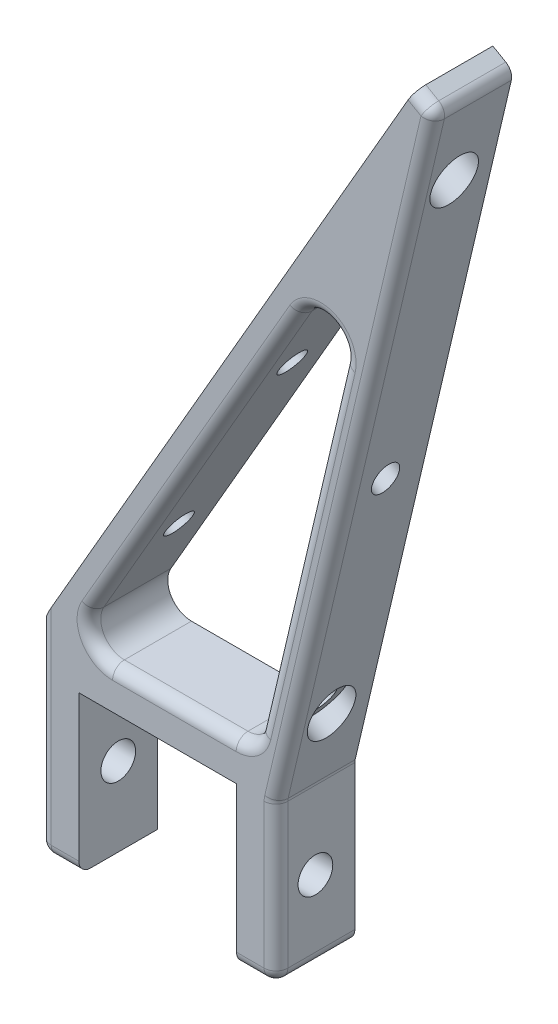
SolidWorks part; units mm, degrees
material "ABS"
ref_plane "Front Plane" through (0, 0, 0) normal (0, 0, 1) x (1, 0, 0)
ref_plane "Top Plane" through (0, 0, 0) normal (0, 1, 0) x (1, 0, 0)
ref_plane "Right Plane" through (0, 0, 0) normal (1, 0, 0) x (0, 0, -1)
sketch "Sketch1" plane through (0, 0, 0) normal (0, 0, 1) x (1, 0, 0)
  line L0 (-10, -20) -> (-10, 0)
  line L1 (-10, 0) -> (10, 0)
  line L2 (10, 0) -> (10, -20)
  line L3 (10, -20) -> (15, -20)
  line L4 (15, -20) -> (15, 0)
  line L5 (15, 0) -> (35.1015, 85.7704)
  line L6 (32.5, 87.2724) -> (-15, 5)
  line L7 (-15, 5) -> (-15, -20)
  line L8 (-15, -20) -> (-10, -20)
  line L9 (32.5, 87.2724) -> (35.1015, 85.7704)
  dimension "D1" = 5
  dimension "D2" = 20
  dimension "D3" = 20
  dimension "D4" = 166.81
  dimension "D5" = 150
  dimension "D6" = 20
  dimension "D7" = 25
  dimension "D8" = 95
extrude "Boss-Extrude1" add sketch "Sketch1" along normal blind 10
sketch "Sketch2" plane through (0, 0, 10) normal (0, 0, 1) x (1, 0, 0)
  line L0 (-10.9175, 5) -> (28.2148, 72.7791)
  line L1 (28.2148, 72.7791) -> (12.3298, 5)
  line L2 (12.3298, 5) -> (-10.9175, 5)
  line L3 (-10, 0) -> (10, 0) construction
  line L5 (15, 0) -> (35.1015, 85.7704) construction
  line L6 (32.5, 87.2724) -> (-15, 5) construction
  dimension "D1" = 5
  dimension "D2" = 3.7406
  dimension "D3" = 3.5356
extrude "Cut-Extrude1" cut sketch "Sketch2" against normal through all
fillet "Fillet1" radius 3 3 edges at (-10.9175, 5, 5) (12.3298, 5, 5) (28.2148, 72.7791, 5)
fillet "Fillet2" radius 1.5 16 edges at (35.1015, 85.7704, 5) (-15, -7.5, 10) (33.8007, 86.5214, 10) (25.0507, 42.8852, 10) (15, -10, 10) (12.5, -20, 10) (-12.5, -20, 10) (21.7651, 56.485, 10) (4.8718, 32.3478, 10) (-8.3194, 6.5, 10) (2.1151, 5, 10) (11.8153, 5.6491, 10) (18.2272, 30.1633, 10) (15, 0, 5) (15, -20, 5) (-15, -20, 5)
sketch "Sketch3" plane through (-15, 0, 0) normal (-1, 0, 0) x (0, 0, 1)
  line L0 (0, 5) -> (0, -18.5) construction
  line L1 (8.5, -20) -> (0, -20) construction
  circle A0 centre (5, -10) radius 2.2
  dimension "D1" = 5
  dimension "D2" = 10
  dimension "D3" = 4.4
extrude "Cut-Extrude2" cut sketch "Sketch3" against normal through all
sketch "Sketch4" plane through (-13.4151, 7.7452, 0) normal (-0.866, 0.5, 0) x (0, 0, 1)
  line L0 (10, 23.3264) -> (0, 23.3264) construction
  line L1 (10, 90.3301) -> (10, -0.1699) construction
  line L2 (0, 91.8301) -> (0, -3.1699) construction
  line L3 (5, 16.0989) -> (5, 23.3264) construction
  line L4 (8.5, 91.8301) -> (0, 91.8301) construction
  circle A0 centre (5, 81.3301) radius 1.75
  circle A1 centre (5, 44.8301) radius 1.75
  circle A2 centre (5, 16.0989) radius 1.75
  dimension "D1" = 3.5
  dimension "D2" = 10.5
  dimension "D3" = 36.5
  dimension "D4" = 28.7312
extrude "Cut-Extrude3" cut sketch "Sketch4" against normal through all
sketch "Sketch5" plane through (-13.4805, 7.6318, 0) normal (0.866, -0.5, 0) x (0, 0, -1)
  circle A0 centre (-5, 81.4611) radius 3
  dimension "D1" = 6
extrude "Cut-Extrude4" cut sketch "Sketch5" along normal through all from offset 3
sketch "Sketch6" plane through (-13.4151, 7.7452, 0) normal (-0.866, 0.5, 0) x (0, 0, 1)
  circle A0 centre (5, 16.0989) radius 3
  dimension "D1" = 6
extrude "Cut-Extrude5" cut sketch "Sketch6" against normal through all from offset 24.38 offset against normal yes
